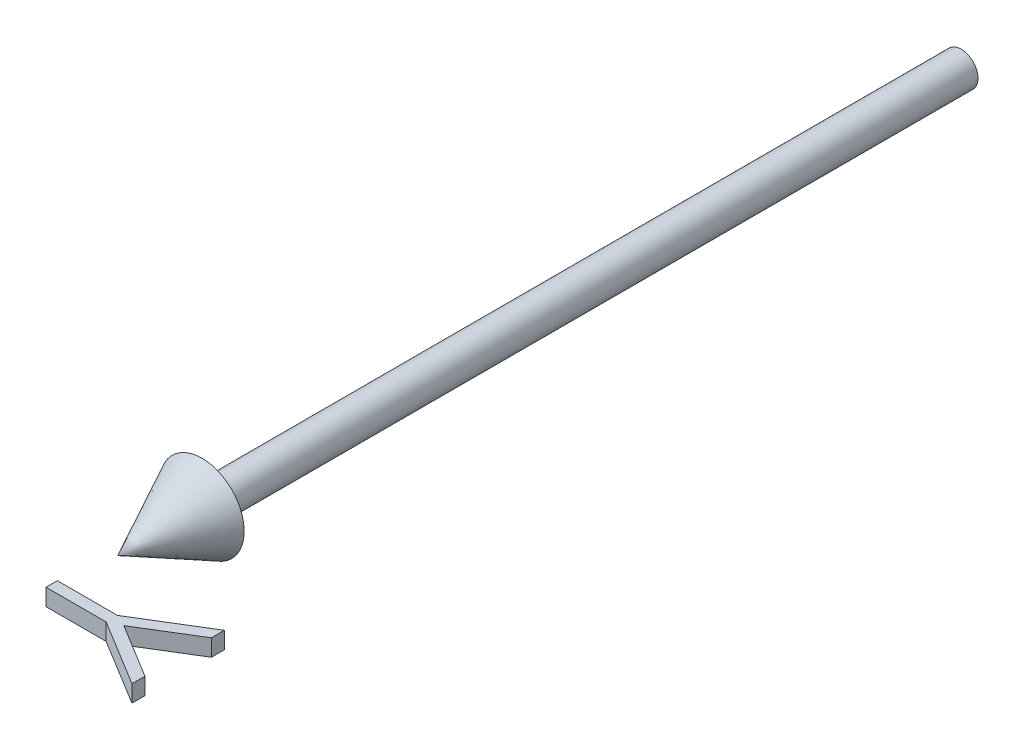
SolidWorks part; units mm, degrees
ref_plane "Front Plane" through (0, 0, 0) normal (0, 0, 1) x (1, 0, 0)
ref_plane "Top Plane" through (0, 0, 0) normal (0, 1, 0) x (1, 0, 0)
ref_plane "Right Plane" through (0, 0, 0) normal (1, 0, 0) x (0, 0, -1)
sketch "Sketch2" plane through (0, 0, 0) normal (0, 1, 0) x (1, 0, 0)
  line L0 (0, 41.95) -> (0, -114.4521) construction
  line L1 (-36.8894, 0) -> (41.4965, 0) construction
  line L2 (0, -100) -> (5, -90)
  line L3 (5, -90) -> (2, -90)
  line L4 (2, -90) -> (2, 0)
  line L5 (2, 0) -> (0, 0)
  line L6 (0, 0) -> (0, -100)
  dimension "D1" = 100
  dimension "D2" = 2
  dimension "D3" = 10
  dimension "D4" = 5
revolve "Revolve1" add sketch "Sketch2" angle 360 about L0
sketch "Sketch3" plane through (0, 0, 0) normal (0, 1, 0) x (1, 0, 0)
  line L0 (0, -101.5706) -> (0, -127.8138) construction
  text T0 "Y" font "Century Gothic" height 15
extrude "Boss-Extrude1" add sketch "Sketch3" against normal blind 1 and the other way blind 1 separate body
equation "\"frame_arrow_length\"=100"
equation "\"D1@Sketch2\"=\"frame_arrow_length\""
equation "\"frame_arrow_odA\"=4"
equation "\"D2@Sketch2\"=\"frame_arrow_odA\"/2"
equation "\"frame_arrow_head_od\"=5"
equation "\"D4@Sketch2\"=\"frame_arrow_head_od\""
equation "\"frame_arrow_head_length\"=10"
equation "\"D3@Sketch2\"=\"frame_arrow_head_length\""
equation "\"tvarobot_theta1\"=30"
equation "\"link0_ringA_odA\"= 40"
equation "\"link0_ringA_odB\"= 25"
equation "\"link0_ringA_id\"= 20"
equation "\"link0_ringA_thickness\"= (\"link0_ringA_odB\" - \"link0_ringA_id\")/2"
equation "\"link0_ringA_height\"= 3"
equation "\"link0_ringA_heightA\"= 1.5"
equation "\"link0_ringA_heightB\"=\"link0_ringA_height\"-\"link0_ringA_heightA\""
equation "\"link0_ringB_odA\"= 40"
equation "\"link0_ringB_odB\"= 29"
equation "\"link0_ringB_id\"= \"link0_shaftA_bearing_id\"+1"
equation "\"link0_ringB_thickness\"= (\"link0_ringB_odB\" - \"link0_ringB_id\")/2"
equation "\"link0_ringB_height\"= 3"
equation "\"link0_ringB_heightA\"= 1.5"
equation "\"link0_ringB_heightB\"=\"link0_ringB_height\"-\"link0_ringB_heightA\""
equation "\"link0_shaftA_bearing_od\"=27"
equation "\"link0_shaftA_bearing_id\"=20"
equation "\"link0_shaftA_thrust_bearing_od\"=35"
equation "\"link0_shaftA_thrust_bearing_id\"=20.04"
equation "\"link0_shaftA_retaining_ring_id\"=18.5"
equation "\"link0_shaftA_retaining_ring_groove_width\"=1.5"
equation "\"link0_shaftA_spline_length\"=8.0"
equation "\"link0_shaftA_spline_depth\"=1.0"
equation "\"link0_shaftA_spline_width\"=4.0"
equation "\"link0_shaftA_odA\"=\"link0_shaftA_bearing_id\""
equation "\"link0_shaftA_odB\"=35"
equation "\"link0_shaftA_odC\"=\"link0_shaftA_bearing_id\""
equation "\"link0_shaftA_odD\"=\"link0_shaftA_odC\"-2*\"link0_shaftA_spline_depth\""
equation "\"link0_shaftA_odE\"=\"link0_shaftA_bearing_id\""
equation "\"link0_shaftA_odF\"=\"link0_shaftA_odE\"-2*\"link0_shaftA_spline_depth\""
equation "\"link0_shaftA_idA\"=10"
equation "\"link0_shaftA_idB\"=6"
equation "\"link0_shaftA_length\"=39.5"
equation "\"link0_shaftA_lengthA\"=8.0"
equation "\"link0_shaftA_lengthB\"=12.0"
equation "\"link0_shaftA_lengthC\"=35.0"
equation "\"link0_shaftA_lengthD\"=39.0"
equation "\"link0_shaftA_lengthE\"=\"link0_shaftA_length\"-\"link0_shaftA_lengthD\""
equation "\"link0_shaftA_offsetX\"=11"
equation "\"link0_shaftA_offsetY\"=0"
equation "\"link0_shaftA_bolt_pattern_dia\"=14"
equation "\"link0_motor_center_dist\"=26"
equation "\"link0_46t_pulley_spline_length\"=8"
equation "\"link0_46t_pulley_spline_depth\"=\"link0_shaftA_spline_depth\"*1.025"
equation "\"link0_46t_pulley_spline_width\"=\"link0_shaftA_spline_width\"*1.05"
equation "\"link0_46t_pulley_idA\"=\"link0_shaftA_bearing_id\"*1.025"
equation "\"link0_46t_pulley_idB\"=\"link0_46t_pulley_idA\"-2*\"link0_46t_pulley_spline_depth\""
equation "\"link0_shaftB_spline_length\"=10"
equation "\"link0_shaftB_spline_depth\"=1.0"
equation "\"link0_shaftB_spline_width\"=1.25"
equation "\"link0_shaftB_length\"=7"
equation "\"link0_shaftB_lengthA\"=1.5"
equation "\"link0_shaftB_lengthB\"=2.75"
equation "\"link0_shaftB_odA\"=32"
equation "\"link0_shaftB_odB\"=22"
equation "\"link0_shaftB_odC\"=20"
equation "\"link0_shaftB_idA\"=10"
equation "\"link0_shaftB_bolt_diameter\"=19"
equation "\"link0_shaftB_bearing_od\"=27"
equation "\"link0_shaftB_bearing_id\"=20"
equation "\"link0_motor_length\"=46.5"
equation "\"link0_motor_width\"=28.5"
equation "\"link0_motor_height\"=34"
equation "\"link0_motor_offset\"=8"
equation "\"link0_shellA_thickness\"=2.5"
equation "\"link0_shellB_thickness\"=\"link0_shellA_thickness\""
equation "\"link0_plateA_shellA_height\"=48"
equation "\"link0_shellA_width\" =\"link0_plateA_width\""
equation "\"link0_shellA_height\" = \"link0_plateA_shellA_height\"-\"link0_plateA_height\""
equation "\"link0_shellA_length\" = \"link0_plateA_lengthB\" "
equation "\"link0_shellB_length\"=\"link0_shellA_length\""
equation "\"link0_shellA_radius\" = 0.375*25.4"
equation "\"link0_shellA_radiusA\"= \"link0_plateA_radiusA\""
equation "\"link0_shellA_radiusB\"= \"link0_plateA_radiusB\""
equation "\"link0_shellA_radiusC\"= 3"
equation "\"link0_postA_height\"=7"
equation "\"link0_postA_width\"=16"
equation "\"link0_postA_length\"=20"
equation "\"link0_postA_posX\"=22"
equation "\"link0_postA_posY\"=17.5"
equation "\"link0_postA_pocket_width\"=6.0"
equation "\"link0_postA_pocket_length\"=2.5"
equation "\"link0_postA_pocket_depth\"=9"
equation "\"link0_postA_pocket_posZ\"=10"
equation "\"link0_postB_height\"=7"
equation "\"link0_postB_width\"=16"
equation "\"link0_postB_length\"=20"
equation "\"link0_postB_posX\"=22"
equation "\"link0_postB_posY\"=17.5"
equation "\"link0_postB_id\"=3.0"
equation "\"link0_postB_pocket_width\"=6.0"
equation "\"link0_postB_pocket_length\"=2.5"
equation "\"link0_postB_pocket_depth\"=9"
equation "\"link0_postB_pocket_posZ\"=10"
equation "\"link0_postC_height\"=7"
equation "\"link0_postC_width\"=16"
equation "\"link0_postC_length\"=20"
equation "\"link0_postC_posX\"=22"
equation "\"link0_postC_posY\"=17.5"
equation "\"link0_postC_id\"=3.0"
equation "\"link0_postC_pocket_width\"=6.0"
equation "\"link0_postC_pocket_length\"=2.5"
equation "\"link0_postC_pocket_depth\"=9"
equation "\"link0_postC_pocket_posZ\"=10"
equation "\"link0_postD_height\"=7"
equation "\"link0_postD_width\"=16"
equation "\"link0_postD_length\"=20"
equation "\"link0_postD_posX\"=22"
equation "\"link0_postD_posY\"=17.5"
equation "\"link0_postD_id\"=3.0"
equation "\"link0_postD_pocket_width\"=6.0"
equation "\"link0_postD_pocket_length\"=3.0"
equation "\"link0_postD_pocket_depth\"=9"
equation "\"link0_postD_pocket_posZ\"=10"
equation "\"link0_postE_height\"=5"
equation "\"link0_postE_width\"=16"
equation "\"link0_postE_length\"=\"link0_plateE_lengthA\"-\"link0_lip_height\""
equation "\"link0_postE_posZ\"=22"
equation "\"link0_postE_posX\"=17.5"
equation "\"link0_postE_posY\"=22"
equation "\"link0_postE_id\"=3.0"
equation "\"link0_postE_cbore_id\"=6.5"
equation "\"link0_postE_hole_id\"=3"
equation "\"link0_postF_posZ\"=22"
equation "\"link0_postF_posX\"=17.5"
equation "\"link0_postF_posY\"=\"link0_plateB_lengthA\"+4"
equation "\"link0_postF_id\"=3.0"
equation "\"link0_postF_cbore_id\"=6.5"
equation "\"link0_postF_hole_id\"=3"
equation "\"link0_postG_posZ\"=22"
equation "\"link0_postG_posX\"=17.5"
equation "\"link0_postG_posY\"=\"link0_plateB_lengthA\"+12"
equation "\"link0_postG_id\"=3.0"
equation "\"link0_postG_cbore_id\"=6.5"
equation "\"link0_postG_hole_id\"=3"
equation "\"link0_postHIJ_posY\"=6"
equation "\"link0_postH_posX\"=28"
equation "\"link0_postH_posY\"=20"
equation "\"link0_postH_posZ\"=20"
equation "\"link0_postH_length\"=10"
equation "\"link0_postI_posX\"=28"
equation "\"link0_postI_posY\"=20"
equation "\"link0_postI_posZ\"=135"
equation "\"link0_postI_length\"=10"
equation "\"link0_postJ_posX\"=28"
equation "\"link0_postJ_posY\"=20"
equation "\"link0_postJ_posZ\"=175"
equation "\"link0_postJ_length\"=10"
equation "\"link0_postK_posX\"=28"
equation "\"link0_postK_posY\"=20"
equation "\"link0_postK_posZ\"=175"
equation "\"link0_postK_length\"=10"
equation "\"link0_postL_posX\"=28"
equation "\"link0_postL_posY\"=20"
equation "\"link0_postL_posZ\"=135"
equation "\"link0_postL_length\"=10"
equation "\"link0_postM_posX\"=28"
equation "\"link0_postM_posY\"=20"
equation "\"link0_postM_posZ\"=35"
equation "\"link0_postM_length\"=10"
equation "\"link0_plateA_lengthA\"=30"
equation "\"link0_plateA_lengthB\"=150"
equation "\"link0_plateA_lengthC\"=30"
equation "\"link0_plateA_length\"=\"link0_plateA_lengthA\"+\"link0_plateA_lengthB\"+\"link0_plateA_lengthC\""
equation "\"link0_plateA_width\"=  68"
equation "\"link0_plateA_height\"= \"link0_plateA_radiusA\""
equation "\"link0_plateA_thickness\"=\"link0_shellA_thickness\""
equation "\"link0_plateA_radius\"= 9.5"
equation "\"link0_plateA_radiusA\"= 18"
equation "\"link0_plateA_radiusB\"= 18"
equation "\"link0_plateA_radiusC\"= 3"
equation "\"link0_plateB_length\"= 40"
equation "\"link0_plateB_width\"= \"link0_plateA_width\"*1.005"
equation "\"link0_plateB_height\"= \"link0_plateA_shellA_height\"*1.005"
equation "\"link0_plateB_lengthA\"=\"link0_lip_height\"+\"link0_plateD_thickness\"+\"link0_motor_mount_thickness\""
equation "\"link0_plateB_lengthB\"=\"link0_plateB_height\"-\"link0_plateB_lengthA\""
equation "\"link0_plateB_radiusA\"= \"link0_plateA_radiusA\""
equation "\"link0_plateB_radiusB\"= \"link0_plateA_radiusB\""
equation "\"link0_plateB_radiusC\"= 3"
equation "\"link0_plateB_idA\"=\"link0_shaftA_odC\"+1"
equation "\"link0_plateB_idB\"=\"link0_shaftA_bearing_od\"-2"
equation "\"link0_plateB_idC\"=\"link0_shaftA_bearing_od\"*1.005"
equation "\"link0_plateB_idD\"=\"link0_shaftA_thrust_bearing_od\"+1 "
equation "\"link0_plateB_depthA\"=1.0"
equation "\"link0_plateB_depthB\"=2.0"
equation "\"link0_plateB_depthC\"=8"
equation "\"link0_plateB_depthD\"=\"link0_plateB_length\"-\"link0_lip_height\"-\"link0_plateD_thickness\" "
equation "\"link0_plateC_length\"=\"link0_plateB_length\""
equation "\"link0_plateC_width\"= \"link0_plateB_width\""
equation "\"link0_plateC_height\"= .1*25.4"
equation "\"link0_plateA_hole_od\" = 0.1*25.4"
equation "\"link0_plateA_hole_delx\" = 0.5*25.4"
equation "\"link0_plateA_hole_delz\" = 0.75*25.4"
equation "\"link0_plateA_hole_offx\" = 0.0*25.4"
equation "\"link0_plateA_hole_offz\" = \"link0_plateA_length\"/2"
equation "\"link0_plateB_hole_od\" = 0.1*25.4"
equation "\"link0_plateB_hole_delx\"= 0.75*25.4"
equation "\"link0_plateB_hole_delz\"= 0.75*25.4"
equation "\"link0_plateB_hole_offx\"= 0.0*25.4"
equation "\"link0_plateB_hole_offz\"= 0.0*25.4"
equation "\"link0_plateC_hole_od\"= 0.1*25.4"
equation "\"link0_plateC_hole_delx\"= 0.75*25.4"
equation "\"link0_plateC_hole_delz\"= 0.75*25.4"
equation "\"link0_plateC_hole_offx\"= 0.0*25.4"
equation "\"link0_plateC_hole_offz\"= 0.0*25.4"
equation "\"link0_plateD_height\"=\"link0_plateB_height\"-2*\"link0_shellA_thickness\""
equation "\"link0_plateD_width\"=\"link0_plateB_width\"-2*\"link0_shellA_thickness\""
equation "\"link0_plateD_thickness\"=10"
equation "\"link0_plateD_radiusA\"=\"link0_plateB_radiusA\"-\"link0_shellA_thickness\""
equation "\"link0_plateD_odA\"= .375*25.4"
equation "\"link0_plateD_odB\"= .375*25.4"
equation "\"link0_plateD_bearing_id\"=20"
equation "\"link0_plateD_bearing_od\"=27"
equation "\"link0_plateE_radiusA\"=\"link0_plateA_radiusA\""
equation "\"link0_plateE_radiusB\"=\"link0_plateA_radiusB\""
equation "\"link0_plateE_radiusC\"=8.0"
equation "\"link0_plateE_length\"=30"
equation "\"link0_plateE_lengthA\"=16"
equation "\"link0_plateE_height\"=\"link0_plateB_height\""
equation "\"link0_plateE_width\"=\"link0_plateB_width\""
equation "\"link0_plateE_odA\"=\"gantry_coupler_id\"*0.99"
equation "\"link0_plateE_idA\"=\"link0_plateE_odA\"-20.0"
equation "\"link0_plateE_spline_depth\"=\"link0_poleA_spline_depth\"*1.05"
equation "\"link0_plateE_spline_width\"=\"link0_poleA_spline_width\"*1.075"
equation "\"link0_plateE_spline_length\"=\"link0_poleA_spline_length\""
equation "\"link0_plateE_coupler_length\"=46"
equation "\"link0_lip_height\"=5.0"
equation "\"link0_lip_thickness\"=2.0"
equation "\"link0_motor_mount_thickness\"=8.0"
equation "\"link0_motor_mount_idA\"=22"
equation "\"link0_motor_mount_idB\"=\"link0_shaftB_bearing_od\"*1.005"
equation "\"link0_motor_mount_idC\"=\"link0_shaftB_bearing_od\"-2"
equation "\"link0_motor_mount_depthA\"=5.5"
equation "\"link0_motor_mount_height\"=\"link0_plateD_height\""
equation "\"link0_motor_mount_width\"=\"link0_plateD_width\""
equation "\"link0_motor_mountL_height\"=36"
equation "\"link0_motor_mountL_heightA\"=12"
equation "\"link0_motor_mountL_length\"=50"
equation "\"link0_motor_mountL_lengthA\"=36"
equation "\"gantry_coupler_od\"=25.4*2.0"
equation "\"gantry_coupler_id\"=1.645*25.4"
equation "\"gantry_coupler_offsetX\"=\"link0_plateE_width\"/2"
equation "\"link0_poleA_odA\"=20"
equation "\"link0_poleA_odB\"=36"
equation "\"link0_poleA_idA\"=\"link0_poleA_odA\"-2*\"link0_poleA_thickness\""
equation "\"link0_poleA_idB\"=(\"link0_plateE_idA\"/2+1.5*\"link0_lip_thickness\")*1.04"
equation "\"link0_poleA_thickness\"=3.5"
equation "\"link0_poleA_length\"=100"
equation "\"link0_poleA_lengthA\"=18.5"
equation "\"link0_poleA_lengthB\"=80"
equation "\"link0_poleA_gasket_thickness\"=1.5"
equation "\"link0_poleA_spline_depth\"=1.0"
equation "\"link0_poleA_spline_width\"=4.0"
equation "\"link0_poleA_spline_length\"=10.0"
equation "\"link1_plateB_length\"=30"
equation "\"link1_lip_height\"=\"link0_lip_height\""
equation "\"link0_tension_plateA_width\"=12"
equation "\"link0_tension_plateA_lengthA\"=10.5"
equation "\"link0_tension_plateB_width\"=\"link0_tension_plateA_width\""
equation "\"link0_tension_plateB_lengthA\"=\"link0_tension_plateA_lengthA\""
equation "\"link0_tension_wheelA_posZ\"=7"
equation "\"link0_tension_wheelA_posX\"=\"link0_plateD_height\"/2-\"link0_tension_plateA_lengthA\""
equation "\"link0_m2_clear_hole_id\"=2.35"
equation "\"link0_m2_insert_hole_id\"=2.5"
equation "\"link0_m2_tap_hole_id\"=1.75"
equation "\"link0_m2_nut_socket_width\"=4.25"
equation "\"link0_m2_nut_socket_depth\"=2.5"
equation "\"link0_m2_cbore_id\"=3.75"
equation "\"link0_m2_cbore_depth\"=7"
equation "\"link0_m2_5_clear_hole_id\"=2.75"
equation "\"link0_m2_5_insert_hole_id\"=2.75"
equation "\"link0_m2_5_tap_hole_id\"=2.25"
equation "\"link0_m2_5_nut_socket_width\"=5.25"
equation "\"link0_m2_5_nut_socket_depth\"=2.5"
equation "\"link0_m2_5_cbore_id\"=4.75"
equation "\"link0_m2_5_cbore_depth\"=2.5"
equation "\"link0_m2_5_insert_access_length\"=6.0"
equation "\"link0_m2_5_insert_access_width\"=3.0"
equation "\"link0_m3_clear_hole_id\"=3.25"
equation "\"link0_m3_insert_hole_id\"=3"
equation "\"link0_m3_tap_hole_id\"=2.75"
equation "\"link0_m3_nut_socket_width\"=5.75"
equation "\"link0_m3_nut_socket_depth\"=4.0"
equation "\"link0_m3_cbore_id\"=5.75"
equation "\"link0_m3_cbore_depth\"=3.5"
equation "\"link0_m3_insert_access_length\"=4.5"
equation "\"link0_m3_insert_access_width\"=3.5"
equation "\"link0_rpi_mount_height\"=6"
equation "\"link0_rpi_mount_width\"=49"
equation "\"link0_rpi_mount_length\"=58"
equation "\"link0_rpi_mount_post_od\"=6"
equation "\"link0_rpi_mount_posZ\"=72"
equation "\"link0_rpi_mount_posX\"=11.5"
equation "\"link0_mcu_mount_height\"=5"
equation "\"link0_mcu_mount_width\"=49"
equation "\"link0_mcu_mount_length\"=58"
equation "\"link0_mcu_mount_post_od\"=6"
equation "\"link0_mcu_mount_posZ\"=164"
equation "\"link0_mcu_mount_posX\"=4"
equation "\"link0_pwr_mount_height\"=4"
equation "\"link0_pwr_mount_width\"=15.75"
equation "\"link0_pwr_mount_length\"=75.75"
equation "\"link0_pwr_mount_post_od\"=6"
equation "\"link0_pwr_mount_posZ\"=75"
equation "\"link0_pwr_mount_posX\"=16"
equation "\"link0_pwr_board_height\"=6"
equation "\"link0_pwr_board_width\"=21"
equation "\"link0_pwr_board_length\"=80"
